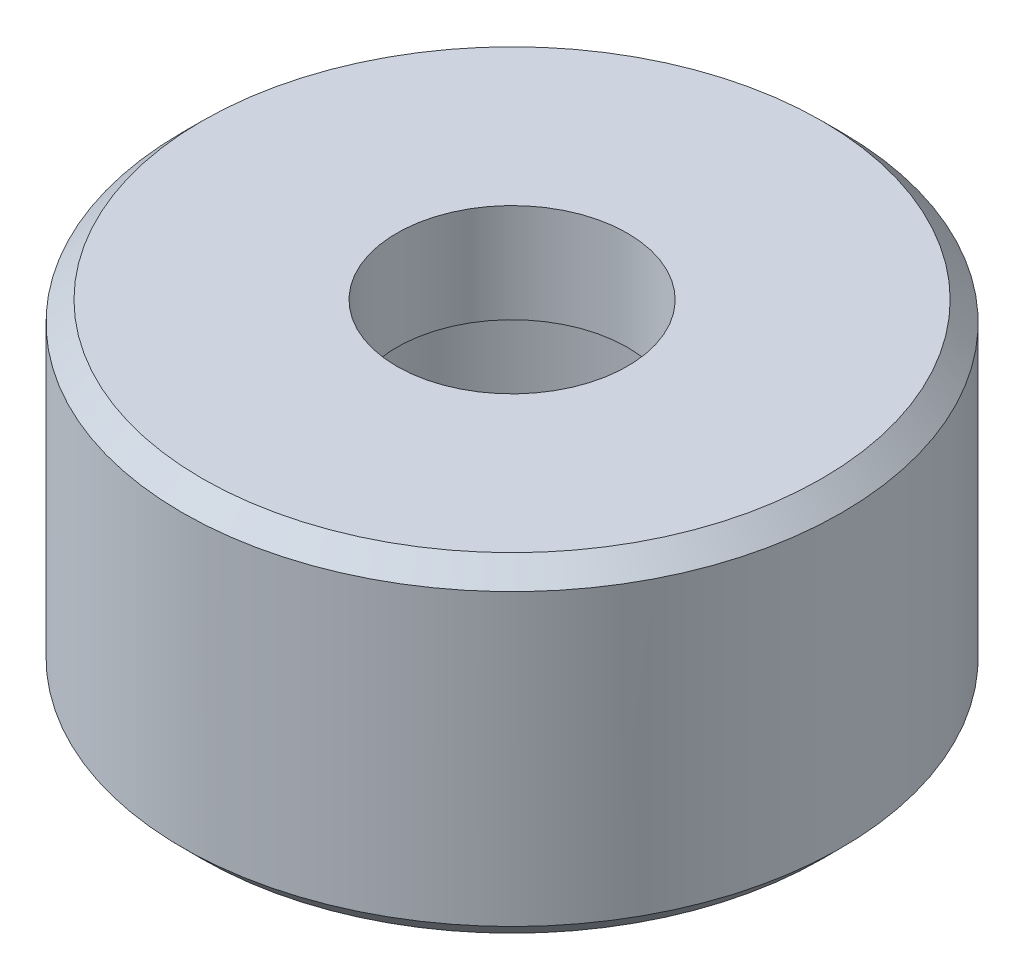
SolidWorks part; units mm, degrees
ref_plane "Front Plane" through (0, 0, 0) normal (0, 0, 1) x (1, 0, 0)
ref_plane "Top Plane" through (0, 0, 0) normal (0, 1, 0) x (1, 0, 0)
ref_plane "Right Plane" through (0, 0, 0) normal (1, 0, 0) x (0, 0, -1)
sketch "Sketch2" plane through (0, 0, 0) normal (1, 0, 0) x (0, 0, -1)
  line L0 (0, 0) -> (0, 14.71) construction
  line L1 (1.75, 5) -> (1.75, 3.5)
  line L2 (1.75, 3.5) -> (3, 3.5)
  line L3 (3, 3.5) -> (3, 0)
  line L4 (3, 0) -> (5, 0)
  line L5 (5, 0) -> (5, 5)
  line L6 (5, 5) -> (1.75, 5)
  point P9 (1.9037, 8.3373)
  dimension "D1" = 6
  dimension "D2" = 3.5
  dimension "D3" = 3.5
  dimension "D4" = 5
  dimension "D5" = 10
revolve "Revolve1" add sketch "Sketch2" angle 360 about L0
chamfer "Chamfer1" distance 0.3 angle 45 2 edges at (0, 0, -5) (0, 5, -5)
